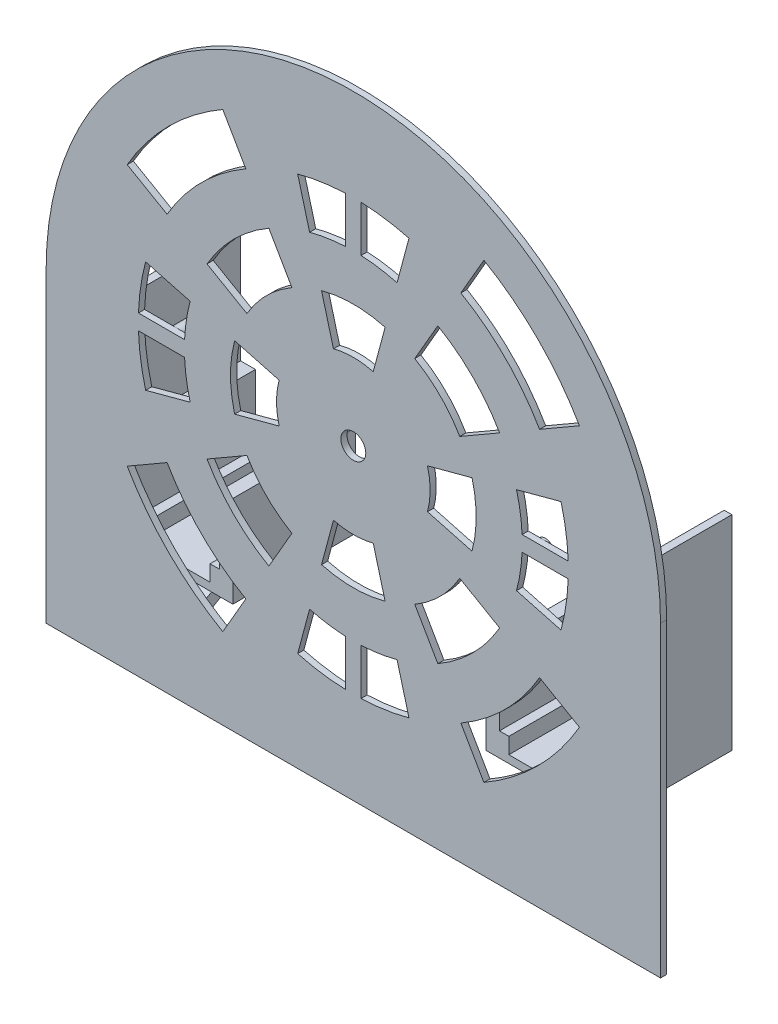
SolidWorks part; units mm, degrees
ref_plane "Front Plane" through (0, 0, 0) normal (0, 0, 1) x (1, 0, 0)
ref_plane "Top Plane" through (0, 0, 0) normal (0, 1, 0) x (1, 0, 0)
ref_plane "Right Plane" through (0, 0, 0) normal (1, 0, 0) x (0, 0, -1)
sketch "Sketch2" plane through (0, 0, 0) normal (0, 0, 1) x (1, 0, 0)
  line L0 (-100, 0) -> (-100, -100)
  line L1 (-100, -100) -> (100, -100)
  line L2 (100, -100) -> (100, 0)
  line L3 (0, 0) -> (0, 100) construction
  line L4 (0, 0) -> (-25.8819, 96.5926) construction
  line L5 (0, 0) -> (25.8819, 96.5926) construction
  line L6 (0, 0) -> (-50, 86.6025) construction
  line L7 (0, 0) -> (-86.6025, 50) construction
  line L8 (6.4705, 24.1481) -> (10.3528, 38.637)
  line L9 (14.235, 53.1259) -> (18.1173, 67.6148)
  line L10 (-18.1173, 67.6148) -> (-14.235, 53.1259)
  line L11 (-10.3528, 38.637) -> (-6.4705, 24.1481)
  line L12 (-20, 34.641) -> (-27.5, 47.6314)
  line L13 (-35, 60.6218) -> (-42.5, 73.6122)
  line L14 (-73.6122, 42.5) -> (-60.6218, 35)
  line L15 (-47.6314, 27.5) -> (-34.641, 20)
  line L16 (42.5, 73.6122) -> (35, 60.6218)
  line L17 (60.6218, 35) -> (73.6122, 42.5)
  line L18 (27.5, 47.6314) -> (20, 34.641)
  line L19 (34.641, 20) -> (47.6314, 27.5)
  line L20 (24.1481, -6.4705) -> (38.637, -10.3528)
  line L21 (38.637, 10.3528) -> (24.1481, 6.4705)
  line L22 (53.1259, -14.235) -> (67.6148, -18.1173)
  line L23 (67.6148, 18.1173) -> (53.1259, 14.235)
  line L24 (73.6122, -42.5) -> (60.6218, -35)
  line L25 (35, -60.6218) -> (42.5, -73.6122)
  line L26 (47.6314, -27.5) -> (34.641, -20)
  line L27 (20, -34.641) -> (27.5, -47.6314)
  line L28 (-6.4705, -24.1481) -> (-10.3528, -38.637)
  line L29 (10.3528, -38.637) -> (6.4705, -24.1481)
  line L30 (-14.235, -53.1259) -> (-18.1173, -67.6148)
  line L31 (18.1173, -67.6148) -> (14.235, -53.1259)
  line L32 (-42.5, -73.6122) -> (-35, -60.6218)
  line L33 (-60.6218, -35) -> (-73.6122, -42.5)
  line L34 (-27.5, -47.6314) -> (-20, -34.641)
  line L35 (-34.641, -20) -> (-47.6314, -27.5)
  line L36 (-24.1481, 6.4705) -> (-38.637, 10.3528)
  line L37 (-38.637, -10.3528) -> (-24.1481, -6.4705)
  line L38 (-53.1259, 14.235) -> (-67.6148, 18.1173)
  line L39 (-67.6148, -18.1173) -> (-53.1259, -14.235)
  arc A0 (100, 0) -> (-100, 0) centre (0, 0) ccw
  circle A1 centre (0, 0) radius 4.05
  arc A2 (6.4705, 24.1481) -> (-6.4705, 24.1481) centre (0, 0) ccw
  arc A3 (10.3528, 38.637) -> (-10.3528, 38.637) centre (0, 0) ccw
  arc A4 (14.235, 53.1259) -> (-14.235, 53.1259) centre (0, 0) ccw
  arc A5 (18.1173, 67.6148) -> (-18.1173, 67.6148) centre (0, 0) ccw
  arc A7 (-42.5, 73.6122) -> (-73.6122, 42.5) centre (0, 0) ccw
  arc A8 (-35, 60.6218) -> (-60.6218, 35) centre (0, 0) ccw
  arc A9 (-27.5, 47.6314) -> (-47.6314, 27.5) centre (0, 0) ccw
  arc A10 (-20, 34.641) -> (-34.641, 20) centre (0, 0) ccw
  arc A11 (60.6218, 35) -> (35, 60.6218) centre (0, 0) ccw
  arc A12 (73.6122, 42.5) -> (42.5, 73.6122) centre (0, 0) ccw
  arc A13 (34.641, 20) -> (20, 34.641) centre (0, 0) ccw
  arc A14 (47.6314, 27.5) -> (27.5, 47.6314) centre (0, 0) ccw
  arc A15 (38.637, -10.3528) -> (38.637, 10.3528) centre (0, 0) ccw
  arc A16 (24.1481, -6.4705) -> (24.1481, 6.4705) centre (0, 0) ccw
  arc A17 (67.6148, -18.1173) -> (67.6148, 18.1173) centre (0, 0) ccw
  arc A18 (53.1259, -14.235) -> (53.1259, 14.235) centre (0, 0) ccw
  arc A19 (35, -60.6218) -> (60.6218, -35) centre (0, 0) ccw
  arc A20 (42.5, -73.6122) -> (73.6122, -42.5) centre (0, 0) ccw
  arc A21 (20, -34.641) -> (34.641, -20) centre (0, 0) ccw
  arc A22 (27.5, -47.6314) -> (47.6314, -27.5) centre (0, 0) ccw
  arc A23 (-10.3528, -38.637) -> (10.3528, -38.637) centre (0, 0) ccw
  arc A24 (-6.4705, -24.1481) -> (6.4705, -24.1481) centre (0, 0) ccw
  arc A25 (-18.1173, -67.6148) -> (18.1173, -67.6148) centre (0, 0) ccw
  arc A26 (-14.235, -53.1259) -> (14.235, -53.1259) centre (0, 0) ccw
  arc A27 (-60.6218, -35) -> (-35, -60.6218) centre (0, 0) ccw
  arc A28 (-73.6122, -42.5) -> (-42.5, -73.6122) centre (0, 0) ccw
  arc A29 (-34.641, -20) -> (-20, -34.641) centre (0, 0) ccw
  arc A30 (-47.6314, -27.5) -> (-27.5, -47.6314) centre (0, 0) ccw
  arc A31 (-38.637, 10.3528) -> (-38.637, -10.3528) centre (0, 0) ccw
  arc A32 (-24.1481, 6.4705) -> (-24.1481, -6.4705) centre (0, 0) ccw
  arc A33 (-67.6148, 18.1173) -> (-67.6148, -18.1173) centre (0, 0) ccw
  arc A34 (-53.1259, 14.235) -> (-53.1259, -14.235) centre (0, 0) ccw
  point P17 (-18.1173, 67.6148)
  point P18 (-14.235, 53.1259)
  point P19 (-10.3528, 38.637)
  point P20 (-6.4705, 24.1481)
  point P21 (6.4705, 24.1481)
  point P22 (10.3528, 38.637)
  point P23 (14.235, 53.1259)
  point P24 (18.1173, 67.6148)
  point P25 (-12.5, 21.6506)
  point P26 (-20, 34.641)
  point P27 (-27.5, 47.6314)
  point P28 (-35, 60.6218)
  point P29 (-42.5, 73.6122)
  point P30 (-73.6122, 42.5)
  point P31 (-60.6218, 35)
  point P32 (-47.6314, 27.5)
  point P33 (-34.641, 20)
  point P34 (-21.6506, 12.5)
  point P97 (0, 0)
  dimension "D1" = 8.1
  dimension "D2" = 100
  dimension "D7" = 50
  dimension "D8" = 80
  dimension "D9" = 110
  dimension "D10" = 140
  dimension "D11" = 4
  dimension "D3" = 15
  dimension "D4" = 15
  dimension "D5" = 15
  dimension "D6" = 30
extrude "Boss-Extrude1" add sketch "Sketch2" along normal blind 2
sketch "Sketch4" plane through (0, 0, 0) normal (0, 0, -1) x (-1, 0, 0)
  line L0 (-76.2223, 0.2395) -> (-76.2223, -63.74) construction
  line L1 (-70.814, -63.74) -> (-48.634, -63.74)
  line L3 (0, 0) -> (0, -100) construction
  line L4 (100, -100) -> (-100, -100) construction
  line L5 (-78.7223, 0.2395) -> (-78.7223, -36.363)
  line L7 (81.2223, -66.24) -> (76.2223, -66.24)
  line L8 (81.2223, 0.2395) -> (81.2223, -66.24)
  line L9 (-81.2223, 0.2395) -> (-81.2223, -66.24)
  line L10 (-81.2223, -66.24) -> (-76.2223, -66.24)
  line L11 (-76.2223, -66.24) -> (-41.2223, -66.24)
  line L12 (81.2223, 0.2395) -> (78.7223, 0.2395)
  line L13 (78.7223, 0.2395) -> (78.7223, -36.363)
  line L14 (-81.2223, 0.2395) -> (-78.7223, 0.2395)
  line L15 (-76.2223, -63.74) -> (76.2179, -63.74) construction
  line L16 (-76.2223, -66.24) -> (76.2179, -66.24) construction
  line L17 (78.7223, -63.74) -> (76.2179, -63.74) construction
  line L18 (78.7223, 0.2395) -> (78.7223, -63.74) construction
  line L19 (81.2223, 0.2395) -> (81.2223, -66.24) construction
  line L20 (81.2223, -66.24) -> (76.2179, -66.24) construction
  line L21 (-41.2223, -63.74) -> (-41.2223, -66.24)
  line L22 (41.2223, -63.74) -> (41.2223, -66.24)
  line L23 (48.634, -63.74) -> (70.814, -63.74)
  line L24 (41.2223, -66.24) -> (76.2223, -66.24)
  line L25 (-78.7223, -36.363) -> (-73.874, -36.363)
  line L26 (-73.874, -36.363) -> (-73.874, -58.54)
  line L27 (-73.874, -58.54) -> (-70.814, -58.54)
  line L28 (-70.814, -58.54) -> (-70.814, -63.74)
  line L29 (-72.374, -57.04) -> (-72.374, -36.14) construction
  line L30 (-72.124, -57.04) -> (-68.424, -57.04) construction
  line L31 (-69.314, -57.04) -> (-69.314, -63.74) construction
  line L32 (-41.2223, -63.74) -> (-41.2223, -36.4105)
  line L33 (-41.2223, -36.4105) -> (-45.574, -36.4105)
  line L34 (-45.574, -36.4105) -> (-45.574, -58.54)
  line L35 (-45.574, -58.54) -> (-48.634, -58.54)
  line L36 (-48.634, -58.54) -> (-48.634, -63.74)
  line L37 (-50.134, -63.74) -> (-50.134, -57.04) construction
  line L38 (-47.074, -57.04) -> (-51.024, -57.04) construction
  line L39 (-47.074, -36.14) -> (-47.074, -57.04) construction
  line L40 (-78.7223, -63.74) -> (-76.2223, -63.74) construction
  line L41 (-78.7223, 0.2395) -> (-78.7223, -63.74) construction
  line L42 (78.7223, -36.363) -> (73.874, -36.363)
  line L43 (73.874, -36.363) -> (73.874, -58.54)
  line L44 (70.814, -58.54) -> (70.814, -63.74)
  line L45 (73.874, -58.54) -> (70.814, -58.54)
  line L46 (48.634, -58.54) -> (48.634, -63.74)
  line L47 (45.574, -58.54) -> (48.634, -58.54)
  line L48 (41.2223, -36.4105) -> (45.574, -36.4105)
  line L49 (45.574, -36.4105) -> (45.574, -58.54)
  line L50 (41.2223, -36.4105) -> (41.2223, -63.74)
  arc A0 (-47.6314, -27.5) -> (-27.5, -47.6314) centre (0, 0) ccw construction
  point P28 (0, -63.74)
  point P30 (0, -66.24)
  point P40 (-72.344, -58.54)
  dimension "D1" = 2.5
  dimension "D3" = 40
  dimension "D4" = 1.5
  dimension "D5" = 1.5
  dimension "D6" = 1.5
  dimension "D7" = 1.5
  dimension "D8" = 1.5
  dimension "D9" = 1.5
  dimension "D2" = 2.5
extrude "Boss-Extrude2" add sketch "Sketch4" along normal blind 40
ref_plane "Plane1" through (63, 0, 0) normal (1, 0, 0) x (0, 0, -1)
sketch "Sketch7" plane through (63, 0, 0) normal (1, 0, 0) x (0, 0, -1)
  line L0 (0, -86.4473) -> (35, -66.24)
  line L1 (0, -100) -> (0, 0) construction
  line L2 (40, -66.24) -> (0, -66.24) construction
  line L3 (0, -81.7509) -> (26.8657, -66.24)
  line L4 (0, -81.7509) -> (0, -86.4473)
  line L5 (26.8657, -66.24) -> (35, -66.24)
  dimension "D1" = 5
extrude "Boss-Extrude3" add sketch "Sketch7" along normal blind 5 and the other way blind 5
mirror "Mirror1" about plane through (0, 0, 0) normal (1, 0, 0) of "Boss-Extrude3"
sketch "Sketch8" plane through (0, 0, 2) normal (0, 0, 1) x (1, 0, 0)
  line L0 (0, 0) -> (-100, 0) construction
  line L1 (-100, 0) -> (-100, -100) construction
  line L2 (-54.9432, 2.5) -> (-69.9553, 2.5)
  line L3 (-54.9432, -2.5) -> (-69.9553, -2.5)
  line L4 (-2.5, 54.9432) -> (-2.5, 69.9553)
  line L5 (2.5, 54.9432) -> (2.5, 69.9553)
  line L6 (54.9432, 2.5) -> (69.9553, 2.5)
  line L7 (54.9432, -2.5) -> (69.9553, -2.5)
  line L8 (2.5, -54.9432) -> (2.5, -69.9553)
  line L9 (-2.5, -54.9432) -> (-2.5, -69.9553)
  arc A0 (-67.6148, 18.1173) -> (-67.6148, -18.1173) centre (0, 0) ccw construction
  arc A1 (-53.1259, 14.235) -> (-53.1259, -14.235) centre (0, 0) ccw construction
  spline S0 degree 2 poles (-54.9432, 2.5) (-55.0568, 0) (-54.9432, -2.5) knots 0 0 0 1 1 1
  spline S1 degree 2 poles (-69.9553, 2.5) (-70.0447, 0) (-69.9553, -2.5) knots 0 0 0 1 1 1
  spline S2 degree 2 poles (2.5, 69.9553) (0, 70.0447) (-2.5, 69.9553) knots 0 0 0 1 1 1
  spline S3 degree 2 poles (2.5, 54.9432) (0, 55.0568) (-2.5, 54.9432) knots 0 0 0 1 1 1
  spline S4 degree 2 poles (69.9553, -2.5) (70.0447, 0) (69.9553, 2.5) knots 0 0 0 1 1 1
  spline S5 degree 2 poles (54.9432, -2.5) (55.0568, 0) (54.9432, 2.5) knots 0 0 0 1 1 1
  spline S6 degree 2 poles (-2.5, -69.9553) (0, -70.0447) (2.5, -69.9553) knots 0 0 0 1 1 1
  spline S7 degree 2 poles (-2.5, -54.9432) (0, -55.0568) (2.5, -54.9432) knots 0 0 0 1 1 1
  point P5 (-69.9553, 2.5)
  point P6 (-54.9432, 2.5)
  point P10 (-55, 0)
  point P14 (-70, 0)
  point P20 (-59.724, 0)
  point P21 (59.724, 0)
  point P42 (0, 0)
  dimension "D1" = 2.5
  dimension "D2" = 2.5
  dimension "D3" = 4
extrude "Boss-Extrude4" add sketch "Sketch8" against normal up to surface (2 mm away) contours S1 L3 S0 L2 | L5 S2 L4 S3 | L6 S4 L7 S5 | L8 S6 L9 S7 up to face at (63, -84.0991, 0)
sketch "Sketch10" plane through (0, 0, 2) normal (0, 0, 1) x (1, 0, 0)
  circle A0 centre (-59.724, 0) radius 2.5
extrude "Boss-Extrude5" add sketch "Sketch10" against normal blind 7
dome "Dome1" faces to dome 1 distance 1 reverse direction no elliptical dome no face at (-57.224, 0, -5) parameters "D1"=1
sketch "Sketch12" plane through (0, 0, 0) normal (0, 0, -1) x (-1, 0, 0)
  circle A0 centre (-59.724, 0) radius 2.5
extrude "Boss-Extrude6" add sketch "Sketch12" along normal blind 0.75
dome "Dome2" faces to dome 1 distance 1 reverse direction no elliptical dome no face at (57.224, 0, -0.75) parameters "D1"=1
ref_plane "Plane2" through (0, 0, -11.5) normal (0, 0, -1) x (-1, 0, 0)
